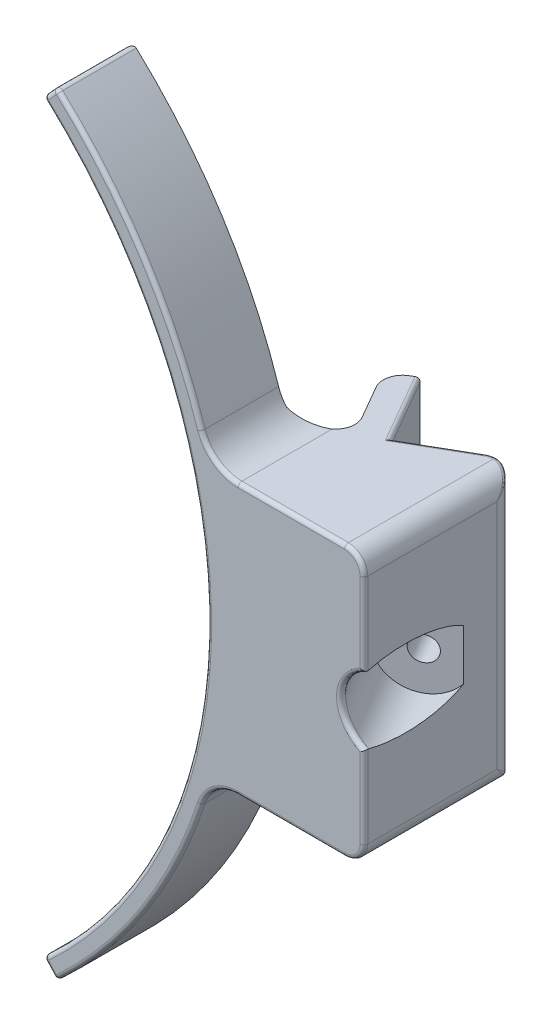
SolidWorks part; units mm, degrees
ref_plane "Front Plane" through (0, 0, 0) normal (0, 0, 1) x (1, 0, 0)
ref_plane "Top Plane" through (0, 0, 0) normal (0, 1, 0) x (1, 0, 0)
ref_plane "Right Plane" through (0, 0, 0) normal (1, 0, 0) x (0, 0, -1)
sketch "Sketch1" plane through (0, 0, 0) normal (0, 1, 0) x (1, 0, 0)
  line L0 (0, 0) -> (0, 20)
  line L1 (0, 20) -> (40, 43.094)
  line L2 (40, 43.094) -> (40, 0)
  line L3 (40, 0) -> (0, 0)
  line L4 (0, 20) -> (81.2789, 20) construction
  dimension "D1" = 30
  dimension "D2" = 40
  dimension "D3" = 20
extrude "Boss-Extrude2" add sketch "Sketch1" along normal blind 70
sketch "Sketch2" plane through (-8.6603, 0, -15) normal (-0.5, 0, -0.866) x (-0.866, 0, 0.5)
  line L0 (-40, 35) -> (-10, 35) construction
  line L1 (-10, 70) -> (-10, 0) construction
  circle A0 centre (-40, 35) radius 3.15
  dimension "D1" = 30
  dimension "D2" = 6.3
extrude "Cut-Extrude1" cut sketch "Sketch2" against normal through all
ref_plane "Plane1" through (-1.1603, 0, -2.0096) normal (-0.5, 0, -0.866) x (-0.866, 0, 0.5)
sketch "Sketch4" plane through (-1.1603, 0, -2.0096) normal (-0.5, 0, -0.866) x (-0.866, 0, 0.5)
  circle A0 centre (-40, 35) radius 10
  dimension "D1" = 20
extrude "Cut-Extrude3" cut sketch "Sketch4" against normal through all
sketch "Sketch5" plane through (0, 0, 0) normal (0, 0, 1) x (1, 0, 0)
  line L0 (-42.9774, -61.3011) -> (-39.6132, -65)
  line L1 (-130.5652, 35) -> (33.4808, 35) construction
  line L2 (-42.9774, 131.3011) -> (-39.6132, 135)
  line L3 (-130.5652, 35) -> (-39.6132, -65) construction
  line L4 (-39.6132, 135) -> (-39.6132, -65) construction
  line L5 (-130.5652, 35) -> (-42.9774, 131.3011) construction
  arc A0 (-42.9774, -61.3011) -> (-42.9774, 131.3011) centre (-130.5652, 35) ccw
  arc A1 (-39.6132, -65) -> (-39.6132, 135) centre (-130.5652, 35) ccw
  ellipse E0 centre (33.4808, 35) end of major axis (33.4808, 31.85) minor radius 2.728 construction
  dimension "D1" = 260.35
  dimension "D2" = 5
  dimension "D3" = 200
extrude "Boss-Extrude3" add sketch "Sketch5" against normal blind 20
sketch "Sketch6" plane through (-8.6603, 0, -15) normal (-0.5, 0, -0.866) x (-0.866, 0, 0.5)
  line L0 (-56.188, 0) -> (-10, 0) construction
  line L1 (-22.95, 70) -> (-29.95, 70)
  line L2 (-22.95, 70) -> (-22.95, 0)
  line L3 (-22.95, 0) -> (-29.95, 0)
  line L4 (-29.95, 70) -> (-29.95, 0)
  line L5 (-29.95, 2.5) -> (-29.95, 67.5) construction
  point P9 (0, 0)
  point P10 (0, 0)
  dimension "D1" = 7
extrude "Boss-Extrude4" add sketch "Sketch6" along normal blind 20
sketch "Sketch7" plane through (19.8753, 0, -11.475) normal (-0.866, 0, 0.5) x (0.5, 0, 0.866)
  circle A0 centre (-29.8205, 12.5) radius 1.25 construction
  circle A1 centre (-29.8205, 57.5) radius 1.25 construction
  circle A2 centre (-29.8205, 12.5) radius 1.25 construction
  circle A3 centre (-29.8205, 57.5) radius 1.25 construction
  circle A4 centre (-29.8205, 12.5) radius 1.5
  circle A5 centre (-29.8205, 57.5) radius 1.5
  dimension "D1" = 3
extrude "Cut-Extrude4" cut sketch "Sketch7" against normal through all
fillet "Fillet1" radius 5 5 edges at (1.215, 35, -43.7955) (40, 0, -21.547) (40, 70, -21.547) (40, 35, -43.094) (11.215, 35, -26.475)
fillet "Fillet2" radius 10 2 edges at (0, 70, -10) (0, 0, -10)
fillet "Fillet3" radius 1 28 edges at (38.5355, 1.4645, -37.9693) (33.7059, 0, -39.2634) (38.5355, 68.5355, -37.9693) (33.7059, 70, -39.2634) (-42.9774, 131.3011, -10) (-41.2953, 133.1505, -20) (-39.6132, 135, -10) (-39.6132, -65, -10) (-41.2953, -63.1505, -20) (-42.9774, -61.3011, -10) (-41.2953, -63.1505, 0) (-0.3902, 35, 0) (-41.2953, 133.1505, 0) (-17.0506, 108.3942, 0) (1.5855, 71.9069, 0) (21.2297, 70, 0) (38.5355, 68.5355, 0) (40, 54.2214, 0) (34.641, 35, 0) (40, 15.7786, 0) (38.5355, 1.4645, 0) (21.2297, 0, 0) (1.5855, -1.9069, 0) (-17.0506, -38.3942, 0) (12.2772, 0, -38.6353) (24.8886, 0, -34.3694) (24.8886, 70, -34.3694) (12.2772, 70, -38.6353)
